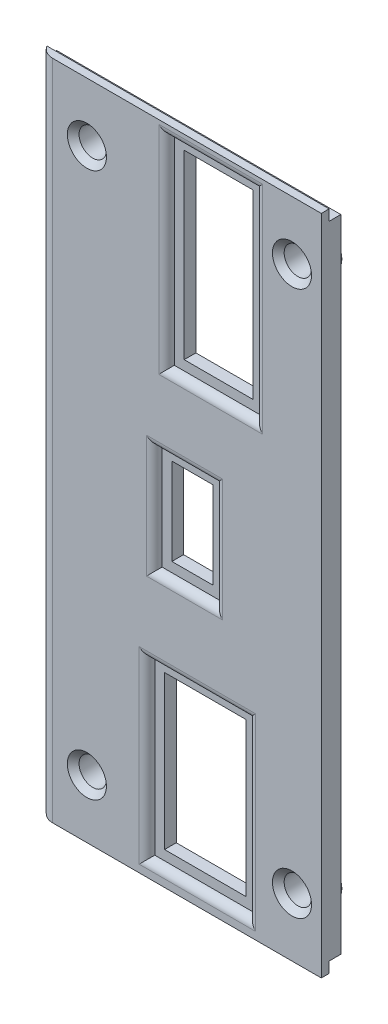
SolidWorks part; units mm, degrees
ref_plane "Спереди" through (0, 0, 0) normal (0, 0, 1) x (1, 0, 0)
ref_plane "Сверху" through (0, 0, 0) normal (0, 1, 0) x (1, 0, 0)
ref_plane "Справа" through (0, 0, 0) normal (1, 0, 0) x (0, 0, -1)
sketch "Эскиз1" plane through (0, 0, 0) normal (0, 0, 1) x (1, 0, 0)
  line L0 (-14.55, 33) -> (14.55, 33)
  line L1 (14.55, 34.1) -> (-14.55, 34.1)
  line L2 (1.832, 31.0818) -> (6.15, 31.0818)
  line L3 (6.15, 31.0818) -> (6.15, 13.7082)
  line L4 (0.308, 16.9213) -> (0.308, 27.8687)
  line L5 (6.15, 13.7082) -> (1.832, 13.7082)
  line L6 (2.05, 2.8885) -> (2.05, -0.4615)
  line L7 (-0.95, -0.4615) -> (-0.95, 2.8885)
  line L8 (-0.95, 2.8885) -> (2.05, 2.8885)
  line L9 (2.05, -12.9615) -> (2.05, -1.4615)
  line L10 (2.05, -4.8115) -> (-0.95, -4.8115)
  line L11 (-0.95, -4.8115) -> (-0.95, -1.4615)
  line L12 (14.55, -34.1) -> (-14.55, -34.1)
  line L13 (-14.55, -33) -> (14.55, -33)
  line L14 (-1.7, -17.9837) -> (-1.7, -28.9837)
  line L15 (0.01, -30.7337) -> (3.71, -30.7337)
  line L16 (5.42, -28.9837) -> (5.42, -23.5087)
  line L17 (5.42, -17.9837) -> (5.42, -23.4587)
  line L18 (3.71, -16.2337) -> (0.01, -16.2337)
  circle A0 centre (-9.45, 27.9) radius 1
  circle A1 centre (11.55, 27.9) radius 1.1
  circle A2 centre (11.55, 27.9) radius 2.1
  circle A3 centre (11.55, -27.9) radius 2.1
  circle A4 centre (11.55, -27.9) radius 1.1
  circle A5 centre (-9.45, -27.9) radius 1
sketch "Эскиз2" plane through (0, 0, 0) normal (0, 0, 1) x (1, 0, 0)
  line L0 (14.55, -34.1) -> (-14.55, -34.1) construction
  line L1 (-14.55, 33.9) -> (14.55, 33.9)
  line L2 (-14.55, 33.9) -> (-14.55, -33.9)
  line L3 (-14.55, -33.9) -> (14.55, -33.9)
  line L4 (14.55, 33.9) -> (14.55, -33.9)
  line L5 (14.55, 34.1) -> (-14.55, 34.1) construction
  dimension "D1" = 0.2
  dimension "D2" = 0.2
extrude "Бобышка-Вытянуть1" add sketch "Эскиз2" along normal blind 0.8
sketch "Эскиз3" plane through (0, 0, 0) normal (0, 0, -1) x (-1, 0, 0)
  line L0 (-14.55, -33.9) -> (-14.55, 33.9) construction
  line L1 (-14.55, 32.8) -> (14.55, 32.8)
  line L2 (-14.55, 32.8) -> (-14.55, -32.8)
  line L3 (-14.55, -32.8) -> (14.55, -32.8)
  line L4 (14.55, 32.8) -> (14.55, -32.8)
  line L5 (14.55, 33.9) -> (14.55, -33.9) construction
  line L6 (14.55, 33) -> (-14.55, 33) construction
  line L7 (14.55, -33) -> (-14.55, -33) construction
  dimension "D1" = 0.2
  dimension "D2" = 0.2
extrude "Бобышка-Вытянуть2" add sketch "Эскиз3" along normal blind 1.2
sketch "Эскиз4" plane through (0, 0, 0.8) normal (0, 0, 1) x (1, 0, 0)
  line L0 (6.15, 31.0818) -> (6.15, 13.7082) construction
  line L1 (6.75, 31.6818) -> (-0.292, 31.6818)
  line L2 (6.75, 31.6818) -> (6.75, 13.1082)
  line L3 (6.75, 13.1082) -> (-0.292, 13.1082)
  line L4 (-0.292, 31.6818) -> (-0.292, 13.1082)
  line L5 (6.15, 13.7082) -> (1.832, 13.7082) construction
  line L6 (0.308, 16.9213) -> (0.308, 27.8687) construction
  line L7 (1.832, 31.0818) -> (6.15, 31.0818) construction
  line L8 (-0.95, 2.8885) -> (2.05, 2.8885) construction
  line L9 (-1.55, 3.4885) -> (2.65, 3.4885)
  line L10 (-1.55, 3.4885) -> (-1.55, -5.4115)
  line L11 (-1.55, -5.4115) -> (2.65, -5.4115)
  line L12 (2.65, 3.4885) -> (2.65, -5.4115)
  line L13 (-2.3, -15.6337) -> (6.02, -15.6337)
  line L14 (-2.3, -15.6337) -> (-2.3, -31.3337)
  line L15 (-2.3, -31.3337) -> (6.02, -31.3337)
  line L16 (6.02, -15.6337) -> (6.02, -31.3337)
  line L17 (2.05, -12.9615) -> (2.05, -1.4615) construction
  line L18 (2.05, -4.8115) -> (-0.95, -4.8115) construction
  line L19 (-0.95, -0.4615) -> (-0.95, 2.8885) construction
  line L20 (3.71, -16.2337) -> (0.01, -16.2337) construction
  line L21 (5.42, -28.9837) -> (5.42, -23.5087) construction
  line L22 (0.01, -30.7337) -> (3.71, -30.7337) construction
  line L23 (-1.7, -17.9837) -> (-1.7, -28.9837) construction
  circle A7 centre (-9.45, -27.9) radius 1.4
  circle A8 centre (11.55, -27.9) radius 1.4
  circle A9 centre (11.55, 27.9) radius 1.4
  circle A10 centre (-9.45, 27.9) radius 1.4
  dimension "D13" = 2.8
  dimension "D1" = 0.6
  dimension "D2" = 0.6
  dimension "D3" = 0.6
  dimension "D4" = 0.6
  dimension "D5" = 0.6
  dimension "D6" = 0.6
  dimension "D7" = 0.6
  dimension "D8" = 0.6
  dimension "D9" = 0.6
  dimension "D10" = 0.6
  dimension "D11" = 0.6
  dimension "D12" = 0.6
extrude "Вырез-Вытянуть1" cut sketch "Эскиз4" against normal through all
sketch "Эскиз5" plane through (0, 0, -1.2) normal (0, 0, -1) x (-1, 0, 0)
  circle A0 centre (-11.55, 27.9) radius 2.1 construction
  circle A1 centre (-11.55, 27.9) radius 2.1
  circle A2 centre (-11.55, -27.9) radius 2.1 construction
  circle A3 centre (-11.55, -27.9) radius 2.1
  circle A4 centre (9.45, 27.9) radius 2.1
  circle A5 centre (9.45, -27.9) radius 2.1
  circle A6 centre (-11.55, 27.9) radius 1.1 construction
  circle A7 centre (-11.55, 27.9) radius 1.1
  circle A8 centre (9.45, 27.9) radius 1 construction
  circle A9 centre (9.45, 27.9) radius 1
  circle A10 centre (9.45, -27.9) radius 1 construction
  circle A11 centre (9.45, -27.9) radius 1
  circle A12 centre (-11.55, -27.9) radius 1.1 construction
  circle A13 centre (-11.55, -27.9) radius 1.1
extrude "Бобышка-Вытянуть3" add sketch "Эскиз5" along normal blind 1
sketch "Эскиз6" plane through (0, 0, -1.2) normal (0, 0, -1) x (-1, 0, 0)
  line L0 (14.55, 32.8) -> (-14.55, 32.8) construction
  line L1 (12.45, 32.8) -> (11.45, 32.8)
  line L2 (12.45, 32.8) -> (12.45, -32.8)
  line L3 (12.45, -32.8) -> (11.45, -32.8)
  line L4 (11.45, 32.8) -> (11.45, -32.8)
  line L5 (-14.55, -32.8) -> (14.55, -32.8) construction
  line L6 (14.55, -32.8) -> (14.55, 32.8) construction
  dimension "D1" = 1
  dimension "D2" = 2.1
extrude "Бобышка-Вытянуть4" add sketch "Эскиз6" along normal blind 1
chamfer "Фаска1" distance 1 angle 45 2 edges at (-11.95, -32.8, -2.2) (-11.95, 32.8, -2.2)
chamfer "Фаска3" distance 1 angle 45 3 edges at (-11.45, -30.6702, -1.2) (-11.45, 30.6702, -1.2) (-11.45, 0, -1.2)
sketch "Эскиз7" plane through (0, 0, 0.8) normal (0, 0, 1) x (1, 0, 0)
  line L0 (6.02, -15.6337) -> (-2.3, -15.6337) construction
  line L1 (-1.292, 32.6818) -> (7.75, 32.6818)
  line L2 (-1.292, 32.6818) -> (-1.292, 12.1082)
  line L3 (-1.292, 12.1082) -> (7.75, 12.1082)
  line L4 (7.75, 32.6818) -> (7.75, 12.1082)
  line L5 (-2.55, 4.4885) -> (3.65, 4.4885)
  line L6 (-2.55, 4.4885) -> (-2.55, -6.4115)
  line L7 (-2.55, -6.4115) -> (3.65, -6.4115)
  line L8 (3.65, 4.4885) -> (3.65, -6.4115)
  line L9 (-3.3, -14.6337) -> (7.02, -14.6337)
  line L10 (-3.3, -14.6337) -> (-3.3, -32.3337)
  line L11 (-3.3, -32.3337) -> (7.02, -32.3337)
  line L12 (7.02, -14.6337) -> (7.02, -32.3337)
  line L13 (6.02, -31.3337) -> (6.02, -15.6337) construction
  line L14 (-2.3, -31.3337) -> (6.02, -31.3337) construction
  line L15 (-2.3, -15.6337) -> (-2.3, -31.3337) construction
  line L16 (-1.55, -5.4115) -> (2.65, -5.4115) construction
  line L17 (-1.55, 3.4885) -> (-1.55, -5.4115) construction
  line L18 (2.65, -5.4115) -> (2.65, 3.4885) construction
  line L19 (2.65, 3.4885) -> (-1.55, 3.4885) construction
  line L20 (-0.292, 13.1082) -> (6.75, 13.1082) construction
  line L21 (6.75, 13.1082) -> (6.75, 31.6818) construction
  line L22 (-0.292, 31.6818) -> (-0.292, 13.1082) construction
  line L23 (6.75, 31.6818) -> (-0.292, 31.6818) construction
  dimension "D1" = 1
  dimension "D2" = 1
  dimension "D3" = 1
  dimension "D4" = 1
  dimension "D5" = 1
  dimension "D6" = 1
  dimension "D7" = 1
  dimension "D8" = 1
  dimension "D9" = 1
  dimension "D10" = 1
  dimension "D11" = 1
  dimension "D12" = 1
extrude "Вырез-Вытянуть2" cut sketch "Эскиз7" against normal blind 0.8
fillet "Скругление3" radius 0.8 4 edges at (3.229, 12.1082, 0.8) (7.75, 22.395, 0.8) (3.229, 32.6818, 0.8) (-1.292, 22.395, 0.8)
fillet "Скругление4" radius 0.8 4 edges at (0.55, -6.4115, 0.8) (-2.55, -0.9615, 0.8) (0.55, 4.4885, 0.8) (3.65, -0.9615, 0.8)
fillet "Скругление5" radius 0.8 4 edges at (1.86, -32.3337, 0.8) (-3.3, -23.4837, 0.8) (1.86, -14.6337, 0.8) (7.02, -23.4837, 0.8)
sketch "Эскиз8" plane through (0, 0, -1.2) normal (0, 0, 1) x (1, 0, 0)
  circle A1 centre (11.55, 27.9) radius 1.4
  circle A2 centre (11.55, 27.9) radius 1.4
  circle A3 centre (-9.45, -27.9) radius 1.4
  circle A4 centre (-9.45, -27.9) radius 1.4
  circle A5 centre (11.55, -27.9) radius 1.4
  circle A6 centre (11.55, -27.9) radius 1.4
  circle A7 centre (-9.45, 27.9) radius 1.4
  circle A8 centre (-9.45, 27.9) radius 1.4
  dimension "D1" = 0
  dimension "D2" = 0
  dimension "D3" = 0
  dimension "D4" = 0
extrude "Вырез-Вытянуть3" cut sketch "Эскиз8" against normal through all
chamfer "Фаска4" distance 0.6 angle 45 4 edges at (12.95, 27.9, 0.8) (12.95, -27.9, 0.8) (-8.05, -27.9, 0.8) (-8.05, 27.9, 0.8)
fillet "Скругление6" radius 1.6 1 edges at (-14.55, 0, 0.8)
